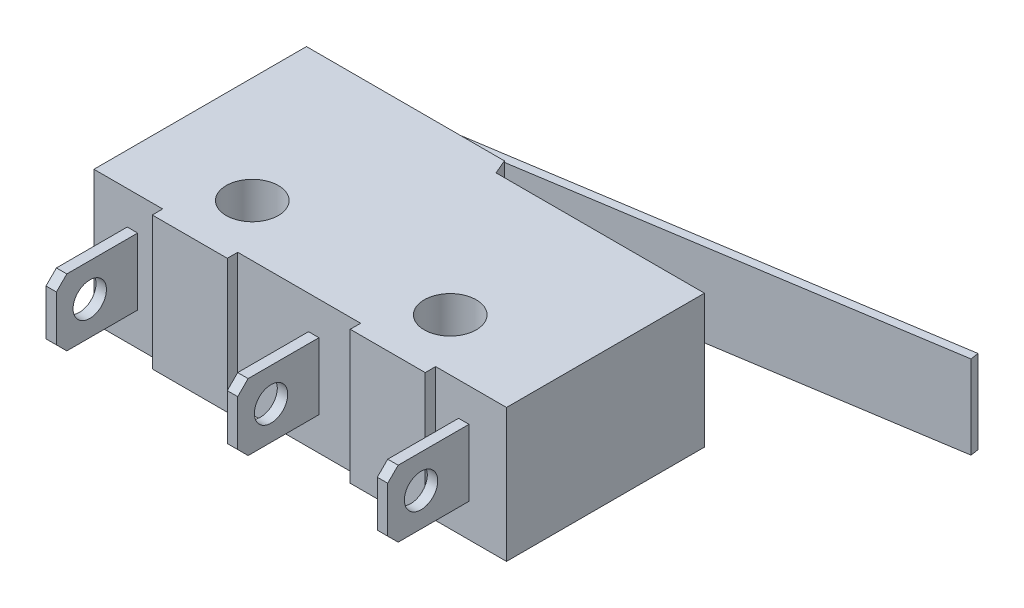
SolidWorks part; units mm, degrees
ref_plane "前基準面" through (0, 0, 0) normal (0, 0, 1) x (1, 0, 0)
ref_plane "上基準面" through (0, 0, 0) normal (0, 1, 0) x (1, 0, 0)
ref_plane "右基準面" through (0, 0, 0) normal (1, 0, 0) x (0, 0, -1)
sketch "草圖1" plane through (0, 0, 0) normal (0, 1, 0) x (1, 0, 0)
  line L5 (-0.4, 5.1) -> (-0.1, 4.4)
  line L6 (9.9, -5.1) -> (-9.9, -5.1)
  line L7 (9.9, -5.1) -> (9.9, 4.4)
  line L8 (-0.4, 5.1) -> (-9.9, 5.1)
  line L9 (-9.9, -5.1) -> (-9.9, 5.1)
  line L10 (9.9, -5.1) -> (-9.9, 5.1) construction
  line L11 (8.5412, 4.4) -> (-9.9, -5.1) construction
  line L12 (-0.1, 4.4) -> (9.9, 4.4)
  line L13 (9.9, 5.1) -> (-0.4, 5.1) construction
  line L14 (9.9, 5.1) -> (8.5412, 4.4) construction
  line L15 (9.9, 4.4) -> (9.9, 5.1) construction
  point P0 (0, 0)
  dimension "D1" = 19.8
  dimension "D2" = 10.2
  dimension "D3" = 9.5
  dimension "D4" = 10
  dimension "D5" = 9.5
extrude "填料-伸長1" add sketch "草圖1" along normal blind 6.4
sketch "草圖3" plane through (0, 6.4, 0) normal (0, 1, 0) x (1, 0, 0)
  line L0 (-9.9, -5.1) -> (9.9, -5.1) construction
  line L1 (-9.9, 5.1) -> (-9.9, -5.1) construction
  circle A0 centre (-4.8, -2.6) radius 1.25
  circle A1 centre (4.7, -2.6) radius 1.25
  dimension "D2" = 2.5
  dimension "D1" = 2.5
  dimension "D3" = 5.1
  dimension "D4" = 9.5
extrude "除料-伸長1" cut sketch "草圖3" against normal through all
ref_axis "基準軸1" through (-4.8, 0, 2.6) along (0, 1, 0)
sketch "草圖4" plane through (-9.9, 0, 0) normal (-1, 0, 0) x (0, 0, 1)
  line L0 (5.1, 6.4) -> (5.1, 0) construction
  line L1 (9, 1.6) -> (5.1, 1.6)
  line L2 (9, 1.6) -> (9, 4.8)
  line L3 (9, 4.8) -> (5.1, 4.8)
  line L4 (5.1, 1.6) -> (5.1, 4.8)
  line L5 (9, 1.6) -> (5.1, 4.8) construction
  line L6 (9, 4.8) -> (5.1, 1.6) construction
  circle A1 centre (7.4, 3.2) radius 0.8
  point P0 (7.05, 3.2)
  point P9 (5.1, 3.2)
  dimension "D3" = 1.6
  dimension "D1" = 3.9
  dimension "D2" = 3.2
  dimension "D4" = 1.6
extrude "填料-伸長2" add sketch "草圖4" against normal blind 0.5 from offset 1.6 offset against normal yes
chamfer "導角1" distance 0.5 angle 45 2 edges at (-8.05, 1.6, 9) (-8.05, 4.8, 9)
pattern_linear "直線複製排列1" count 2 spacing 8.7 along (1, 0, 0) count 2 spacing 15.9 along (1, 0, 0) of "導角1", "填料-伸長2" pattern seed only yes
ref_plane "平面4" through (0, 3.2, 0) normal (0, 1, 0) x (1, 0, 0)
sketch "草圖5" plane through (0, 3.2, 0) normal (0, 1, 0) x (1, 0, 0)
  line L0 (-6.9, 5.1) -> (-6.9, 5.6)
  line L1 (-0.4, 5.1) -> (-9.9, 5.1) construction
  line L2 (-6.9, 5.6) -> (17.8, 9.4613)
  line L3 (-9.9, 5.1) -> (-9.9, -5.1) construction
  circle A0 centre (-4.8, -2.6) radius 1.25 construction
  dimension "D1" = 3
  dimension "D2" = 22.6
  dimension "D3" = 25
  dimension "D4" = 0.5
sketch "草圖6" plane through (0, 0, -5.1) normal (0, 0, -1) x (-1, 0, 0)
  line L1 (6.7, 1.2) -> (7.1, 1.2)
  line L2 (6.7, 1.2) -> (6.7, 5.2)
  line L3 (6.7, 5.2) -> (7.1, 5.2)
  line L4 (7.1, 1.2) -> (7.1, 5.2)
  line L5 (6.7, 1.2) -> (7.1, 5.2) construction
  line L6 (6.7, 5.2) -> (7.1, 1.2) construction
  line L7 (9.9, 6.4) -> (9.9, 0) construction
  point P0 (6.9, 3.2)
  point P7 (9.9, 3.2)
  dimension "D1" = 0.4
  dimension "D2" = 3
  dimension "D3" = 4
sweep "掃出1" add profiles "草圖6" path "草圖5"
ref_axis "基準軸2" through (4.7, 0, 2.6) along (0, 1, 0)
ref_axis "基準軸3" through (-4.8, 0, 2.6) along (0, 1, 0)
sketch "草圖7" plane through (0, 0, 5.1) normal (0, 0, 1) x (1, 0, 0)
  line L0 (4.7, 0) -> (4.7, 6.4) construction
  line L1 (-6.6, 0) -> (-3, 0)
  line L2 (-6.6, 0) -> (-6.6, 6.4)
  line L3 (-6.6, 6.4) -> (-3, 6.4)
  line L4 (-3, 0) -> (-3, 6.4)
  line L5 (-6.6, 0) -> (-3, 6.4) construction
  line L6 (-6.6, 6.4) -> (-3, 0) construction
  line L10 (-9.9, 6.4) -> (9.9, 6.4) construction
  line L11 (2.9, 0) -> (6.5, 0)
  line L12 (2.9, 0) -> (2.9, 6.4)
  line L13 (2.9, 6.4) -> (6.5, 6.4)
  line L14 (6.5, 0) -> (6.5, 6.4)
  line L15 (2.9, 0) -> (6.5, 6.4) construction
  line L16 (2.9, 6.4) -> (6.5, 0) construction
  line L17 (-4.8, 0) -> (-4.8, 6.4) construction
  line L18 (-9.9, 0) -> (9.9, 0) construction
  point P0 (-4.8, 3.2)
  point P13 (4.7, 3.2)
  dimension "D2" = 3.6
  dimension "D3" = 2
extrude "填料-伸長4" add sketch "草圖7" along normal blind 0.5
